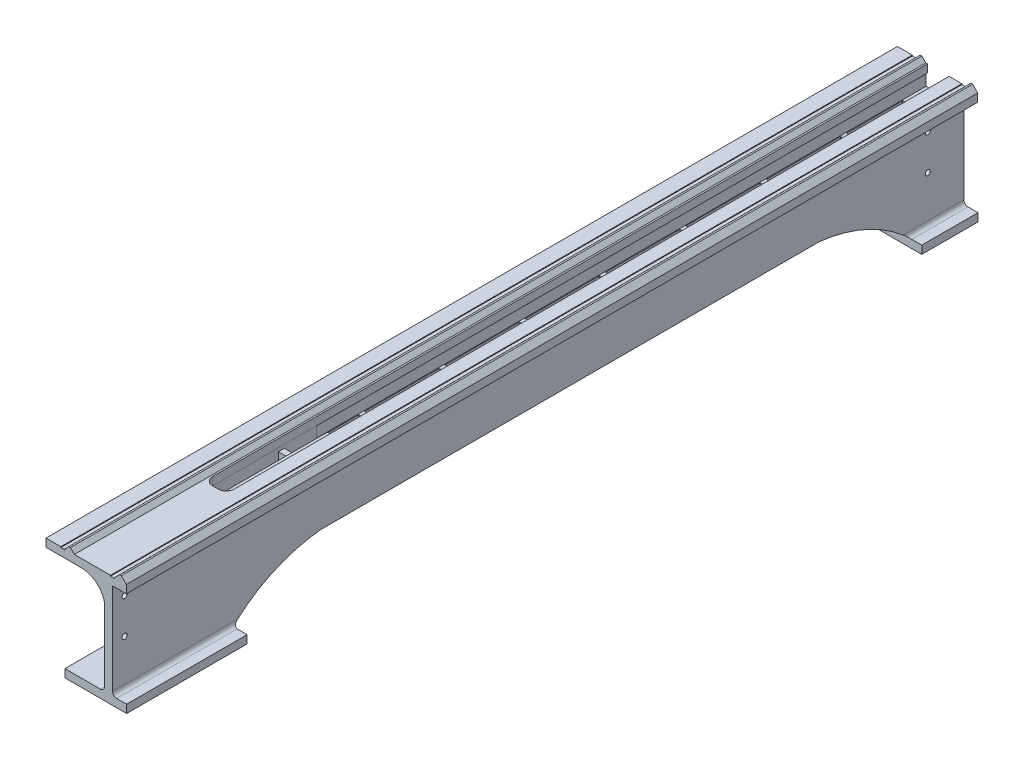
SolidWorks part; units mm, degrees
ref_plane "Front Plane" through (0, 0, 0) normal (0, 0, 1) x (1, 0, 0)
ref_plane "Top Plane" through (0, 0, 0) normal (0, 1, 0) x (1, 0, 0)
ref_plane "Right Plane" through (0, 0, 0) normal (1, 0, 0) x (0, 0, -1)
sketch "Sketch1" plane through (0, 0, 0) normal (0, 0, 1) x (1, 0, 0)
  line L0 (-31.5551, 31.2902) -> (-37.8538, 37.7187)
  line L2 (-131.555, 31.42) -> (-131.555, 21.42)
  line L4 (-31.5551, 31.2902) -> (-31.5551, 21.2902)
  line L5 (-37.8538, 37.7187) -> (-39.8538, 37.7187)
  line L6 (-39.8538, 37.7187) -> (-46.2824, 31.42)
  line L7 (-46.2824, 31.42) -> (-46.2824, 30.42)
  line L8 (-46.2824, 30.42) -> (-51.2824, 30.42)
  line L9 (-51.2824, 30.42) -> (-51.2824, 31.42)
  line L10 (-51.2824, 31.42) -> (-96.2063, 31.42)
  line L14 (-96.2063, 31.42) -> (-101.1053, 36.42)
  line L15 (-101.1053, 36.42) -> (-103.1053, 36.42)
  line L16 (-103.1053, 36.42) -> (-108.055, 31.4703)
  line L17 (-108.055, 31.4703) -> (-108.055, 30.42)
  line L18 (-108.055, 30.42) -> (-113.055, 30.42)
  line L19 (-113.055, 30.42) -> (-113.055, 31.42)
  line L20 (-113.055, 31.42) -> (-131.555, 31.42)
  line L21 (-131.555, 21.42) -> (-87.3496, 21.42)
  line L22 (-31.5551, 21.2902) -> (-48.7011, 21.2902)
  line L23 (-48.7011, 21.2902) -> (-48.7011, -92.58)
  line L24 (-43.7011, -97.58) -> (-31.1954, -97.58)
  line L25 (-31.1954, -97.58) -> (-31.1954, -107.58)
  line L26 (-31.1954, -107.58) -> (-108.01, -107.58)
  line L27 (-108.01, -107.58) -> (-108.01, -97.58)
  line L28 (-108.01, -97.58) -> (-63.7011, -97.58)
  line L29 (-58.7011, -92.58) -> (-58.7011, -1.9527)
  arc A0 (-87.3496, 21.42) -> (-58.7011, -1.9527) centre (-87.3496, -7.8239) cw
  arc A1 (-48.7011, -92.58) -> (-43.7011, -97.58) centre (-43.7011, -92.58) ccw
  arc A2 (-63.7011, -97.58) -> (-58.7011, -92.58) centre (-63.7011, -92.58) ccw
  point P30 (-48.7011, -97.58)
  dimension "D17" = 5
  dimension "D1" = 100
  dimension "D2" = 7
  dimension "D3" = 2
  dimension "D4" = 5
  dimension "D5" = 18.5
  dimension "D6" = 5
  dimension "D7" = 10
  dimension "D8" = 135
  dimension "D9" = 9
  dimension "D10" = 9
  dimension "D11" = 2
  dimension "D12" = 7
  dimension "D13" = 10
  dimension "D14" = 5
  dimension "D15" = 10
  dimension "D16" = 139
  dimension "D18" = 10
  dimension "D19" = 1
extrude "Boss-Extrude1" add sketch "Sketch1" along normal blind 1060
sketch "Sketch2" plane through (0, 20.7647, 0) normal (0, 1, 0) x (1, 0, 0)
  line L0 (-94.1707, -1200) -> (-94.1707, 0) construction
  line L1 (-84.1707, 100) -> (-77.1707, 100)
  line L2 (-94.1707, 90) -> (-94.1707, -890)
  line L3 (-84.1707, -900) -> (-77.1707, -900)
  line L4 (-67.1707, 90) -> (-67.1707, -890)
  line L5 (-67.1707, -1200) -> (-67.1707, 0) construction
  line L6 (-51.2824, 0) -> (-96.2063, 0) construction
  arc A0 (-94.1707, -890) -> (-84.1707, -900) centre (-84.1707, -890) ccw
  arc A1 (-77.1707, -900) -> (-67.1707, -890) centre (-77.1707, -890) ccw
  arc A2 (-77.1707, 100) -> (-67.1707, 90) centre (-77.1707, 90) cw
  arc A3 (-84.1707, 100) -> (-94.1707, 90) centre (-84.1707, 90) ccw
  point P12 (-67.1707, -900)
  point P15 (-67.1707, 100)
  point P18 (-94.1707, 100)
  dimension "D2" = 10
  dimension "D1" = 1000
  dimension "D3" = 100
extrude "Cut-Extrude1" cut sketch "Sketch2" along normal blind 800
sketch "Sketch5" plane through (0, 0, 0) normal (0, 0, -1) x (-1, 0, 0)
  line L1 (105.3464, -97.4955) -> (94.9198, -97.4955)
  line L2 (105.3464, -97.4955) -> (105.3464, 27.7967)
  line L3 (105.3464, 27.7967) -> (94.9198, 27.7967)
  line L4 (94.9198, -97.4955) -> (94.9198, 27.7967)
extrude "Boss-Extrude2" add sketch "Sketch5" against normal blind 950
sketch "Sketch6" plane through (-105.3464, 0, 0) normal (-1, 0, 0) x (0, 0, 1)
  line L0 (0, -97.4955) -> (0, 21.42) construction
  line L1 (0, 16.5847) -> (7.4351, 16.5847)
  line L2 (0, 16.5847) -> (0, -47.4448)
  line L3 (0, -47.4448) -> (7.4351, -47.4448)
  line L4 (7.4351, 16.5847) -> (7.4351, -47.4448)
extrude "Boss-Extrude3" add sketch "Sketch6" against normal blind 50
pattern_linear "LPattern1" count 10 spacing 100 along (0, 0, 1) of "Boss-Extrude3"
sketch "Sketch4" plane through (-31.5551, 0, 0) normal (1, 0, 0) x (0, 0, -1)
  line L0 (-910, -97.58) -> (-910, -107.58)
  line L1 (-1060, -97.58) -> (0, -97.58) construction
  line L2 (-1060, -107.58) -> (0, -107.58) construction
  line L3 (-910, -107.58) -> (-910, -177.9566)
  line L4 (-910, -177.9566) -> (-70, -177.9566)
  line L5 (-70, -177.9566) -> (-70, -97.58)
  line L6 (-800, -47.58) -> (-180.0688, -47.58)
  line L7 (0, -92.58) -> (0, 21.2902) construction
  line L8 (-1060, -92.58) -> (-1060, 21.2902) construction
  arc A1 (-800, -47.58) -> (-910, -97.58) centre (-783.4011, -230.0975) ccw
  arc A2 (-180.0688, -47.58) -> (-70, -97.58) centre (-201.6096, -241.1508) cw
  dimension "D1" = 60
  dimension "D2" = 70
  dimension "D3" = 150
  dimension "D4" = 110
  dimension "D5" = 110.0688
extrude "Cut-Extrude3" cut sketch "Sketch4" against normal blind 100 and the other way blind 10
sketch "Sketch3" plane through (0, 0, 1060) normal (0, 0, 1) x (1, 0, 0)
  line L0 (-51.2824, 31.42) -> (-96.2063, 31.42) construction
  line L1 (-58.7011, 6.42) -> (-95.7995, 6.42)
  line L2 (-58.7011, 6.42) -> (-58.7011, 21.42)
  line L3 (-58.7011, 21.42) -> (-95.7995, 21.42)
  line L4 (-95.7995, 6.42) -> (-95.7995, 21.42)
  line L5 (-58.7011, -1.9527) -> (-58.7011, -47.4448) construction
  dimension "D1" = 15
  dimension "D2" = 10
extrude "Cut-Extrude2" cut sketch "Sketch3" against normal blind 1000 from offset 300 offset against normal yes
sketch "Sketch7" plane through (0, 0, 0) normal (0, 0, -1) x (-1, 0, 0)
  line L0 (58.7011, 6.42) -> (95.7995, 6.42) construction
  line L1 (99.7499, 6.42) -> (57.7636, 6.42)
  line L2 (99.7499, 6.42) -> (99.7499, -7.7909)
  line L3 (99.7499, -7.7909) -> (57.7636, -7.7909)
  line L4 (57.7636, 6.42) -> (57.7636, -7.7909)
extrude "Boss-Extrude4" add sketch "Sketch7" against normal blind 30
sketch "Sketch8" plane through (0, 6.42, 0) normal (0, 1, 0) x (1, 0, 0)
  circle A0 centre (-79.7891, -14.9723) radius 3.8743
extrude "Cut-Extrude4" cut sketch "Sketch8" against normal blind 30
sketch "Эскиз1" plane through (-48.7011, 0, 0) normal (1, 0, 0) x (0, 0, -1)
  line L0 (0, -92.58) -> (0, 21.2902) construction
  line L1 (-1060, 21.2902) -> (0, 21.2902) construction
  circle A0 centre (-45, 3.2902) radius 3.1675
  dimension "D1" = 45
  dimension "D2" = 18
extrude "Вырез-Вытянуть1" cut sketch "Эскиз1" against normal blind 10
pattern_linear "Линейный массив1" count 2 spacing 44 along (0, -1, 0) count 2 spacing 1000 along (0, 0, 1) of "Вырез-Вытянуть1"
